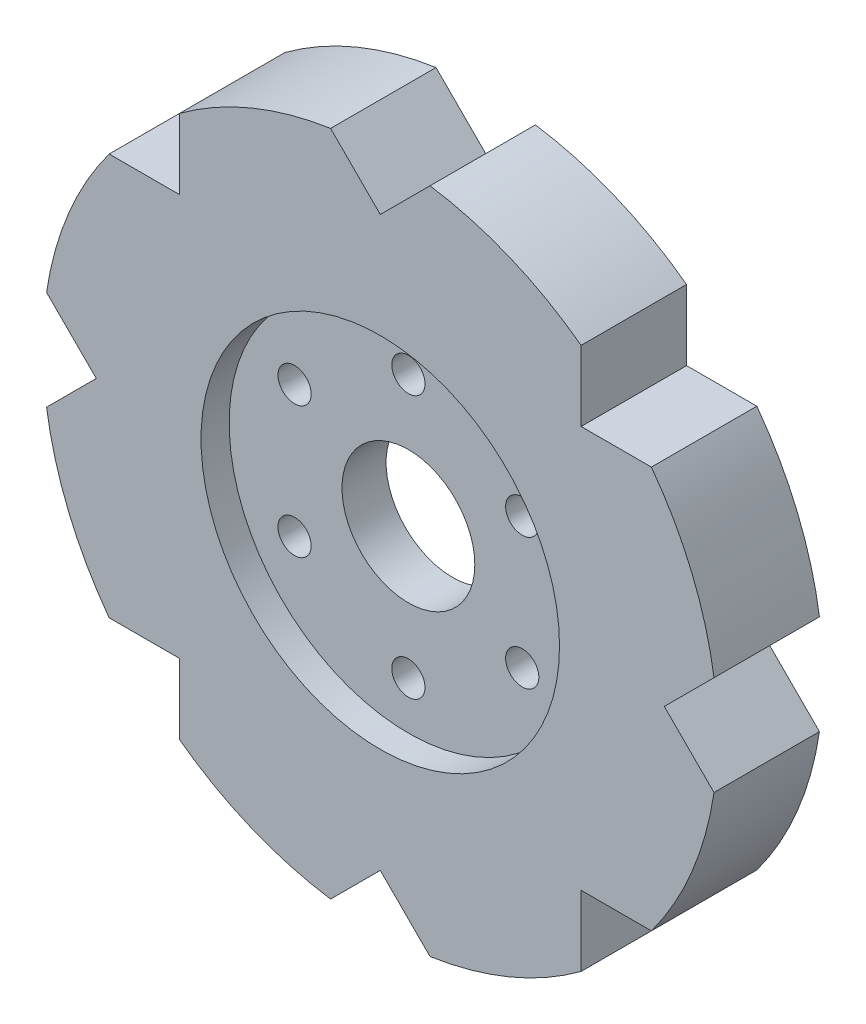
SolidWorks part; units mm, degrees
material "PE High Density Film"
ref_plane "Front Plane" through (0, 0, 0) normal (0, 0, 1) x (1, 0, 0)
ref_plane "Top Plane" through (0, 0, 0) normal (0, 1, 0) x (1, 0, 0)
ref_plane "Right Plane" through (0, 0, 0) normal (1, 0, 0) x (0, 0, -1)
sketch "Sketch1" plane through (0, 0, 0) normal (0, 0, 1) x (1, 0, 0)
  line L0 (0, 0) -> (0, 60.96) construction
  line L1 (-8.9803, 60.2949) -> (0, 51.3147)
  line L2 (0, 51.3147) -> (8.9803, 60.2949)
  line L3 (36.2849, 48.9849) -> (36.2849, 36.2849)
  line L4 (36.2849, 36.2849) -> (48.9849, 36.2849)
  line L5 (60.2949, 8.9803) -> (51.3147, 0)
  line L6 (51.3147, 0) -> (60.2949, -8.9803)
  line L7 (48.9849, -36.2849) -> (36.2849, -36.2849)
  line L8 (36.2849, -36.2849) -> (36.2849, -48.9849)
  line L9 (8.9803, -60.2949) -> (0, -51.3147)
  line L10 (0, -51.3147) -> (-8.9803, -60.2949)
  line L11 (-36.2849, -48.9849) -> (-36.2849, -36.2849)
  line L12 (-36.2849, -36.2849) -> (-48.9849, -36.2849)
  line L13 (-60.2949, -8.9803) -> (-51.3147, 0)
  line L14 (-51.3147, 0) -> (-60.2949, 8.9803)
  line L15 (-48.9849, 36.2849) -> (-36.2849, 36.2849)
  line L16 (-36.2849, 36.2849) -> (-36.2849, 48.9849)
  arc A0 (-60.2949, -8.9803) -> (-48.9849, -36.2849) centre (0, 0) ccw
  arc A1 (-48.9849, 36.2849) -> (-60.2949, 8.9803) centre (0, 0) ccw
  arc A2 (-36.2849, -48.9849) -> (-8.9803, -60.2949) centre (0, 0) ccw
  arc A3 (8.9803, -60.2949) -> (36.2849, -48.9849) centre (0, 0) ccw
  arc A4 (48.9849, -36.2849) -> (60.2949, -8.9803) centre (0, 0) ccw
  arc A5 (60.2949, 8.9803) -> (48.9849, 36.2849) centre (0, 0) ccw
  arc A6 (36.2849, 48.9849) -> (8.9803, 60.2949) centre (0, 0) ccw
  arc A7 (-8.9803, 60.2949) -> (-36.2849, 48.9849) centre (0, 0) ccw
  point P30 (0, 0)
  dimension "D1" = 121.92
  dimension "D2" = 45
  dimension "D3" = 12.7
  dimension "D4" = 8
extrude "Boss-Extrude1" add sketch "Sketch1" along normal blind 19.05
sketch "Sketch2" plane through (0, 0, 19.05) normal (0, 0, 1) x (1, 0, 0)
  circle A0 centre (0, 0) radius 12
  dimension "D1" = 24
extrude "Cut-Extrude1" cut sketch "Sketch2" against normal through all contours A0 region at (0, 0, 19.05)
sketch "Sketch3" plane through (0, 0, 19.05) normal (0, 0, 1) x (1, 0, 0)
  circle A0 centre (0, 0) radius 32.385
  dimension "D1" = 64.77
extrude "Cut-Extrude2" cut sketch "Sketch3" against normal blind 5.08
sketch "Sketch4" plane through (0, 0, 0) normal (0, 0, -1) x (-1, 0, 0)
  circle A0 centre (0, 0) radius 28.4
  dimension "D1" = 56.8
extrude "Cut-Extrude3" cut sketch "Sketch4" against normal blind 6
sketch "Sketch5" plane through (0, 0, 6) normal (0, 0, -1) x (-1, 0, 0)
  line L0 (0, 0) -> (0, 23.75) construction
  circle A0 centre (0, 0) radius 23.75 construction
  circle A1 centre (0, 23.75) radius 2.6
  circle A2 centre (20.5681, 11.875) radius 2.6
  circle A3 centre (20.5681, -11.875) radius 2.6
  circle A4 centre (0, -23.75) radius 2.6
  circle A5 centre (-20.5681, -11.875) radius 2.6
  circle A6 centre (-20.5681, 11.875) radius 2.6
  point P17 (0, 0)
  dimension "D1" = 47.5
  dimension "D2" = 5.2
  dimension "D3" = 6
hole_wizard "Ø6.0mm Dowel Hole1" positions "Sketch6" profile "Sketch8" hole size "Ø6.0" standard "ANSI Metric" end condition through all
sketch "Sketch6" plane through (0, 0, 6) normal (0, 0, -1) x (-1, 0, 0)
  point P0 (0, 23.75)
  point P3 (20.5681, 11.875)
  point P6 (20.5681, -11.875)
  point P9 (0, -23.75)
  point P13 (-20.5681, 11.875)
  point P16 (-20.5681, -11.875)
sketch "Sketch8" plane through (0, 23.75, 6) normal (1, 0, 0) x (0, 1, 0)
  line L0 (0, 0) -> (0, 13.05)
  line L1 (0, 13.05) -> (3, 13.05)
  line L2 (3, 13.05) -> (3, 0)
  line L5 (3, 0) -> (0, 0)
  line L11 (0, -6.35) -> (0, 107.95) construction
  dimension "Thru Hole Dia." = 6
  dimension "Thru Hole Depth" = 13.05
ref_plane "Plane1" through (0, 0, 9.525) normal (0, 0, -1) x (-1, 0, 0)
sketch "Sketch9" plane through (0, 0, 9.525) normal (0, 0, -1) x (-1, 0, 0)
  line L0 (0, 0) -> (23.3284, 56.3197) construction
  line L1 (20.2908, 48.9864) -> (11.4909, 52.6315) construction
  line L2 (17.2533, 41.6531) -> (8.4533, 45.2982)
  line L3 (8.4533, 45.2982) -> (14.5284, 59.9648)
  line L4 (14.5284, 59.9648) -> (32.1283, 52.6746)
  line L5 (32.1283, 52.6746) -> (26.0532, 38.008)
  line L6 (26.0532, 38.008) -> (17.2533, 41.6531)
  arc A0 (36.2849, 48.9849) -> (8.9803, 60.2949) centre (0, 0) ccw construction
  circle A1 centre (20.2908, 48.9864) radius 3.4925
  dimension "D1" = 6.985
  dimension "D2" = 7.9375
  dimension "D3" = 19.05
extrude "Cut-Extrude4" [suppressed] cut sketch "Sketch9" against normal mid plane 11.1125
sketch "Sketch10" [suppressed] plane through (0, 0, 0) normal (0, 0, -1) x (-1, 0, 0)
  circle A0 centre (20.2908, 48.9864) radius 3.4925
  circle A1 centre (20.2908, 48.9864) radius 3.4925 construction
extrude "Cut-Extrude5" [suppressed] cut sketch "Sketch10" against normal through all
sketch "Sketch11" plane through (0, 0, 9.525) normal (0, 0, -1) x (-1, 0, 0)
  line L0 (0, 0) -> (0, 50.8) construction
  line L1 (0, 38.1) -> (-15.875, 38.1)
  line L2 (-15.875, 38.1) -> (-15.875, 63.5)
  line L3 (-15.875, 63.5) -> (15.875, 63.5)
  line L4 (15.875, 63.5) -> (15.875, 38.1)
  line L5 (15.875, 38.1) -> (0, 38.1)
  line L6 (0, 50.8) -> (-15.875, 50.8) construction
  line L7 (0, 0) -> (25.4, 0) construction
  dimension "D1" = 25.4
  dimension "D2" = 90
  dimension "D3" = 31.75
  dimension "D4" = 25.4
  dimension "D5" = 50.8
extrude "Cut-Extrude6" [suppressed] cut sketch "Sketch11" against normal mid plane 11.1125
equation "\"D2@Sketch9\"=0.3125"
